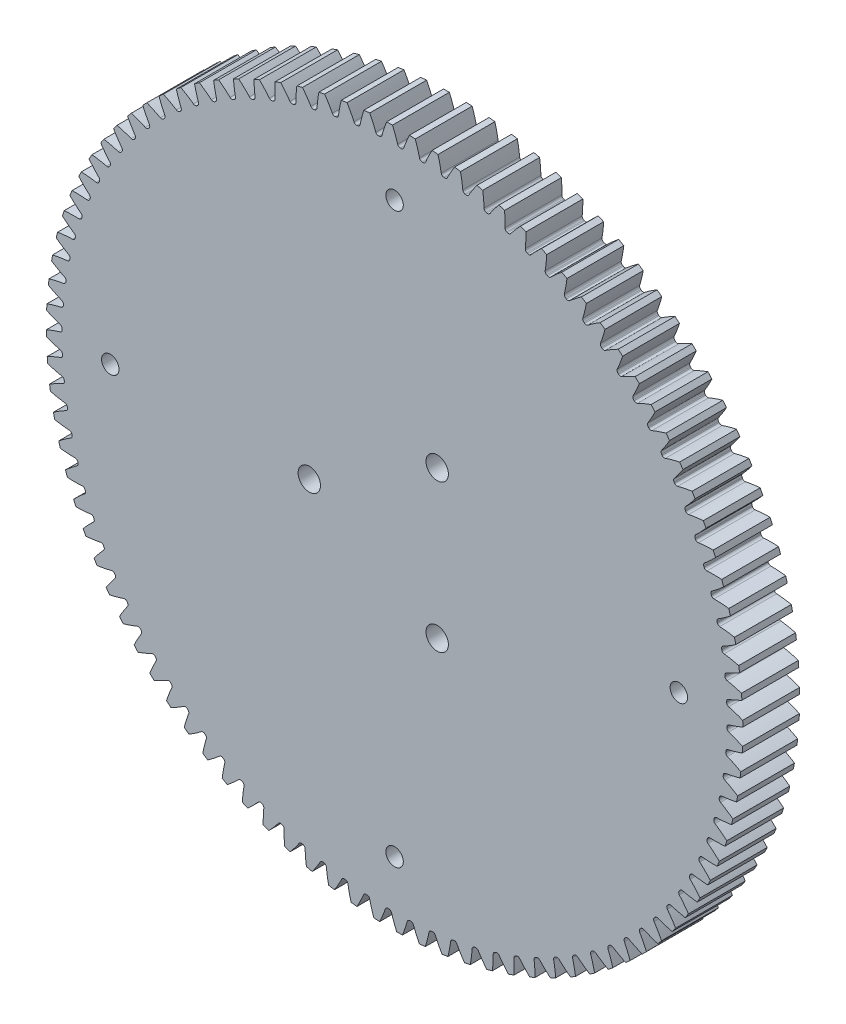
SolidWorks part; units mm, degrees
ref_plane "Front" through (0, 0, 0) normal (0, 0, 1) x (1, 0, 0)
ref_plane "Top" through (0, 0, 0) normal (0, 1, 0) x (1, 0, 0)
ref_plane "Right" through (0, 0, 0) normal (1, 0, 0) x (0, 0, -1)
sketch "Sketch3" plane through (0, 0, 0) normal (0, 0, 1) x (1, 0, 0)
  circle A0 centre (0, 0) radius 77.7875
  dimension "od" = 155.575
extrude "gearBody" add sketch "Sketch3" along normal blind 12.7
sketch "Sketch2" plane through (0, 0, 0) normal (0, 0, 1) x (1, 0, 0)
  line L0 (0, 0) -> (66.154, 27.4019) construction
  line L1 (89.9379, -14.1817) -> (0, 0) construction
  line L2 (0, 0) -> (36.3143, 0) construction
  line L3 (76.1998, -0.172) -> (76.1546, -2.6294) construction
  line L5 (76.1772, -1.4007) -> (0, 0) construction
  line L7 (0, 0) -> (71.6046, 0) construction
  arc A0 (71.5902, -1.4371) -> (71.5946, -1.1957) centre (0, 0) ccw construction
  arc A1 (77.7861, 0.4588) -> (77.7167, -3.3181) centre (0, 0) ccw construction
  arc A2 (76.1998, -0.172) -> (76.1546, -2.6294) centre (0, 0) ccw construction
  arc A3 (74.2296, -1.47) -> (74.2335, -1.2598) centre (0, 0) ccw
  arc A4 (89.9379, -14.1817) -> (74.6441, -2.0632) centre (65.1019, -29.8153) ccw
  arc A5 (89.9379, -14.1817) -> (90.3984, 10.8657) centre (0, 0) ccw
  arc A6 (90.3984, 10.8657) -> (74.6695, -0.6823) centre (66.154, 27.4019) cw
  arc A7 (74.2335, -1.2598) -> (74.6695, -0.6823) centre (74.8478, -1.2702) cw
  arc A8 (74.6441, -2.0632) -> (74.2296, -1.47) centre (74.8439, -1.4822) cw
  point P6 (90.3984, 10.8657)
  point P22 (89.9379, -14.1817)
  dimension "baseDia" = 143.2092
  dimension "od" = 155.575
  dimension "pd" = 152.4
  dimension "rd" = 148.4884
  dimension "rFillet" = 0.6144
  dimension "pointX" = 90.3984
  dimension "pointY" = 10.8657
  dimension "CTT" = 2.4574
  dimension "flankCenterAngle" = 22.5
extrude "toothCut" cut sketch "Sketch2" along normal through all
pattern_circular "CirPattern1" count 96 over 360 about axis through (0, 0, 12.7) along (0, 0, -1) of "toothCut"
sketch "hub1Dia" plane through (0, 0, 0) normal (0, 0, -1) x (-1, 0, 0)
  circle A0 centre (0, 0) radius 12.7
  dimension "hub1Dia" = 25.4
sketch "hub2Dia" plane through (0, 0, 12.7) normal (0, 0, 1) x (1, 0, 0)
  circle A0 centre (0, 0) radius 12.7
  dimension "hub2dia" = 25.4
sketch "boreDia" plane through (0, 0, 0) normal (0, 0, 1) x (1, 0, 0)
  circle A0 centre (0, 0) radius 7.9375
  dimension "boreDia" = 15.875
sketch "Sketch4" plane through (0, 0, 0) normal (0, 0, -1) x (-1, 0, 0)
  circle A0 centre (19.05, 0) radius 2.5
  circle A1 centre (-9.525, -16.4978) radius 2.5
  circle A2 centre (-9.525, 16.4978) radius 2.5
  point P10 (0, 0)
  dimension "D2" = 5
  dimension "D1" = 19.05
  dimension "D3" = 3
extrude "Cut-Extrude1" cut sketch "Sketch4" against normal through all
sketch "Sketch5" plane through (0, 0, 0) normal (0, 0, -1) x (-1, 0, 0)
  circle A0 centre (63.5, 0) radius 1.95
  circle A1 centre (0, -63.5) radius 1.95
  circle A2 centre (-63.5, 0) radius 1.95
  circle A3 centre (0, 63.5) radius 1.95
  point P12 (0, 0)
  dimension "D1" = 3.9
  dimension "D2" = 63.5
  dimension "D3" = 4
extrude "Cut-Extrude2" cut sketch "Sketch5" against normal through all
equation "\"D2@Sketch4\"=5mm"
equation "\"D1@Sketch5\"=3.9mm"
